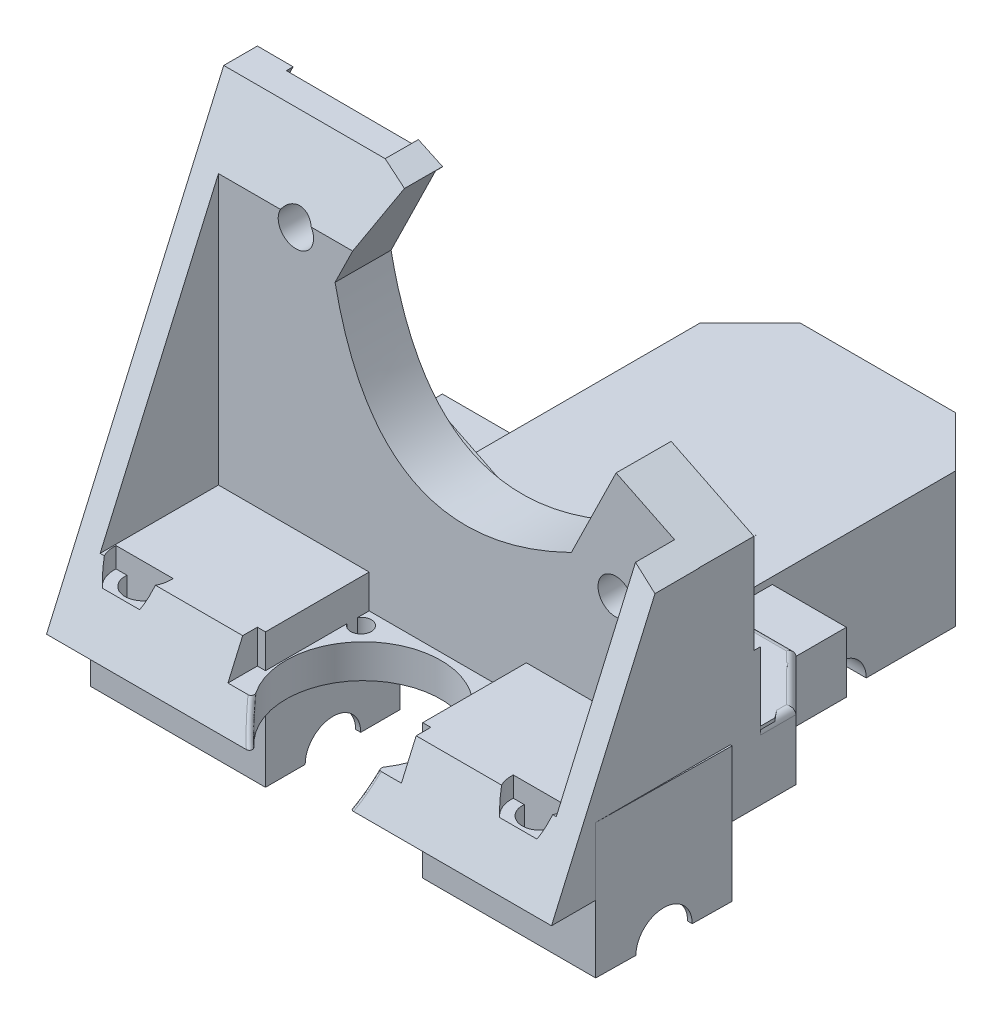
SolidWorks part; units mm, degrees
ref_plane "Front Plane" through (0, 0, 0) normal (0, 0, 1) x (1, 0, 0)
ref_plane "Top Plane" through (0, 0, 0) normal (0, 1, 0) x (1, 0, 0)
ref_plane "Right Plane" through (0, 0, 0) normal (1, 0, 0) x (0, 0, -1)
sketch "Sketch1" plane through (0, 0, 0) normal (0, 1, 0) x (1, 0, 0)
  line L0 (-36.3571, 0) -> (-17.8571, 0)
  line L1 (-36.3571, -43.7952) -> (38.6429, -43.7952)
  line L2 (-36.3571, -43.7952) -> (-36.3571, 0)
  line L3 (-17.8571, 42.2048) -> (20.1429, 42.2048)
  line L4 (38.6429, -43.7952) -> (38.6429, 0)
  line L5 (-36.3571, -43.7952) -> (20.1429, 24.2638) construction
  line L6 (-17.8571, 20.2381) -> (38.6429, -43.7952) construction
  line L7 (-17.8571, 0) -> (-17.8571, 42.2048)
  line L8 (38.6429, 0) -> (20.1429, 0)
  line L9 (20.1429, 0) -> (20.1429, 42.2048)
  line L10 (1.1429, 42.2048) -> (1.1429, -43.7952) construction
  point P0 (0, 0)
  dimension "D1" = 75
  dimension "D2" = 86
  dimension "D3" = 38
  dimension "D4" = 18.5
extrude "Boss-Extrude1" add sketch "Sketch1" along normal blind 10
sketch "Sketch2" plane through (0, 10, 0) normal (0, 1, 0) x (1, 0, 0)
  line L0 (-17.8571, 42.2048) -> (-17.8571, 0) construction
  line L1 (-16.3571, 21) -> (18.6429, 21) construction
  line L2 (11.6429, 41) -> (11.6429, 35.2097) construction
  line L3 (-9.3571, 41) -> (-9.3571, 35.5) construction
  line L4 (2.1863, 41) -> (-16.3571, 41) construction
  line L5 (-16.3571, 41) -> (-16.3571, 1) construction
  line L6 (-16.3571, 1) -> (18.6429, 1) construction
  line L7 (18.6429, 1) -> (18.6429, 41) construction
  line L8 (18.6429, 41) -> (2.1863, 41) construction
  line L9 (11.6429, 1) -> (11.6429, 6.7903) construction
  line L10 (-9.3571, 1) -> (-9.3571, 6.5) construction
  line L11 (-17.8571, 0) -> (-36.3571, 0) construction
  circle A0 centre (-9.3571, 35.5) radius 2.625
  circle A1 centre (-9.3571, 6.5) radius 2.625
  circle A2 centre (11.6429, 6.7903) radius 2.625
  circle A3 centre (11.6429, 35.2097) radius 2.625
  dimension "D7" = 5.25
  dimension "D8" = 5.25
  dimension "D9" = 5.25
  dimension "D10" = 5.25
  dimension "D1" = 40
  dimension "D2" = 35
  dimension "D3" = 1.5
  dimension "D4" = 5.5
  dimension "D5" = 7
  dimension "D6" = 7
  dimension "D11" = 1
extrude "Cut-Extrude1" cut sketch "Sketch2" against normal through all
sketch "Sketch5" plane through (0, 10, 0) normal (0, 1, 0) x (1, 0, 0)
  line L0 (-17.8571, 0) -> (-17.8571, -3) construction
  line L1 (-0.3571, -3) -> (-35.3571, -3) construction
  line L2 (-35.3571, -3) -> (-35.3571, -43) construction
  line L3 (-35.3571, -43) -> (-0.3571, -43) construction
  line L4 (2.6429, -43) -> (2.6429, -3) construction
  line L5 (2.6429, -43) -> (37.6429, -43) construction
  line L6 (20.1429, 0) -> (20.1429, -3) construction
  line L8 (-0.3571, -43) -> (-0.3571, -3) construction
  line L9 (-36.3571, 0) -> (-36.3571, -43.7952) construction
  line L10 (37.6429, -3) -> (37.6429, -43) construction
  line L11 (2.6429, -3) -> (37.6429, -3) construction
  line L12 (38.6429, -43.7952) -> (38.6429, 0) construction
  line L14 (-28.3571, -3) -> (-28.3571, -8.5) construction
  line L15 (-7.3571, -3) -> (-7.3571, -8.5) construction
  line L16 (9.6429, -3) -> (9.6429, -8.5) construction
  line L17 (30.6429, -3) -> (30.6429, -8.5) construction
  line L18 (-35.3571, -23) -> (37.6429, -23) construction
  line L19 (30.6429, -43) -> (30.6429, -37.5) construction
  line L20 (9.6429, -43) -> (9.6429, -37.5) construction
  line L21 (-7.3571, -43) -> (-7.3571, -37.5) construction
  line L22 (-28.3571, -43) -> (-28.3571, -37.5) construction
  circle A0 centre (-28.3571, -8.5) radius 2.625
  circle A1 centre (-7.3571, -8.5) radius 2.625
  circle A2 centre (9.6429, -8.5) radius 2.625
  circle A3 centre (30.6429, -8.5) radius 2.625
  circle A4 centre (30.6429, -37.5) radius 2.625
  circle A5 centre (9.6429, -37.5) radius 2.625
  circle A6 centre (-7.3571, -37.5) radius 2.625
  circle A7 centre (-28.3571, -37.5) radius 2.625
  dimension "D17" = 5.25
  dimension "D18" = 5.25
  dimension "D19" = 5.25
  dimension "D20" = 5.25
  dimension "D1" = 3
  dimension "D2" = 40
  dimension "D3" = 40
  dimension "D4" = 3
  dimension "D5" = 35
  dimension "D6" = 35
  dimension "D7" = 1
  dimension "D8" = 1
  dimension "D9" = 5.5
  dimension "D10" = 5.5
  dimension "D11" = 5.5
  dimension "D12" = 5.5
  dimension "D13" = 7
  dimension "D14" = 7
  dimension "D15" = 7
  dimension "D16" = 7
extrude "Cut-Extrude2" cut sketch "Sketch5" against normal through all
sketch "Sketch7" plane through (0, 10, 0) normal (0, 1, 0) x (1, 0, 0)
  line L1 (-36.3571, -12.4772) -> (38.6429, -12.7296)
  line L2 (-36.3571, -12.4772) -> (-36.3571, -21.8366)
  line L3 (-36.3571, -21.8366) -> (38.6429, -21.8366)
  line L4 (38.6429, -12.7296) -> (38.6429, -21.8366)
  line L5 (38.6429, -43.7952) -> (38.6429, 0) construction
extrude "Boss-Extrude2" add sketch "Sketch7" along normal blind 50
sketch "Sketch8" plane through (-0.0424, 0, 12.5994) normal (0.0034, 0, -1) x (-1, 0, -0.0034)
  line L0 (-31.9124, 60) -> (-31.9124, 38.3732) construction
  line L1 (-38.6855, 60) -> (36.3149, 60) construction
  line L2 (0, 60) -> (0, 10) construction
  line L3 (-20.0007, 10) -> (17.9991, 10) construction
  line L4 (-31.9124, 38.3732) -> (27.3877, 67.3662)
  line L5 (27.3877, 67.3662) -> (35.5135, 50.7463)
  line L6 (30.9221, 37.3702) -> (-22.9803, 11.0163)
  line L7 (-36.3563, 15.6077) -> (-44.4821, 32.2276)
  line L8 (-44.4821, 32.2276) -> (-31.9124, 38.3732)
  line L9 (-38.6855, 10) -> (36.3149, 10) construction
  arc A1 (-22.9803, 11.0163) -> (-36.3563, 15.6077) centre (-27.3726, 20) cw
  arc A2 (35.5135, 50.7463) -> (30.9221, 37.3702) centre (26.5298, 46.3539) cw
  dimension "D1" = 10
  dimension "D2" = 10
  dimension "D3" = 80
  dimension "D4" = 28.5
extrude "Cut-Extrude3" cut sketch "Sketch8" against normal blind 1
sketch "Sketch9" plane through (-0.0458, 0, 13.5994) normal (0.0034, 0, -1) x (-1, 0, -0.0034)
  line L1 (12.3215, 60) -> (-38.6888, 35.06) construction
  line L2 (-9.0128, 49.5692) -> (1.4284, 22.9502) construction
  line L3 (-22.9803, 11.0163) -> (30.9221, 37.3702) construction
  line L9 (33.537, 54.789) -> (21.2078, 48.761) construction
  line L10 (35.5135, 50.7463) -> (30.9892, 60) construction
  circle A0 centre (-26.291, 25.1554) radius 2.625
  circle A1 centre (21.2078, 48.761) radius 2.625
  circle A2 centre (-3.7922, 36.2597) radius 10
  dimension "D5" = 5.25
  dimension "D6" = 5.25
  dimension "D8" = 20
  dimension "D1" = 25
  dimension "D4" = 14
  dimension "D7" = 25
extrude "Cut-Extrude4" cut sketch "Sketch9" against normal through all
chamfer "Chamfer1" distance 7.5 angle 45 4 edges at (20.1429, 5, -42.2048) (-17.8571, 5, -42.2048) (38.6429, 5, 0) (-36.3571, 5, 0)
fillet "Fillet3" radius 1 11 edges at (34.8929, 10, 3.75) (25.6429, 10, 0) (20.1429, 10, -17.3524) (16.3929, 10, -38.4548) (1.1429, 10, -42.2048) (-14.1071, 10, -38.4548) (-17.8571, 10, -17.3524) (-23.3571, 10, 0) (-32.6071, 10, 3.75)
sketch "Sketch15" plane through (0, 10, 0) normal (0, 1, 0) x (1, 0, 0)
  circle A0 centre (-9.3571, 35.5) radius 4.25
  circle A1 centre (11.6429, 35.2097) radius 4.25
  circle A2 centre (-9.3571, 6.5) radius 4.25
  circle A3 centre (11.6429, 6.7903) radius 4.25
  circle A4 centre (-28.3571, -8.5) radius 4.25
  circle A5 centre (-7.3571, -8.5) radius 4.25
  circle A6 centre (9.6429, -8.5) radius 4.25
  circle A7 centre (30.6429, -8.5) radius 4.25
  circle A8 centre (-28.3571, -37.5) radius 4.25
  circle A9 centre (-7.3571, -37.5) radius 4.25
  circle A10 centre (9.6429, -37.5) radius 4.25
  circle A11 centre (30.6429, -37.5) radius 4.25
  dimension "D1" = 8.5
  dimension "D2" = 8.5
  dimension "D3" = 8.5
  dimension "D4" = 8.5
  dimension "D5" = 8.5
  dimension "D6" = 8.5
  dimension "D7" = 8.5
  dimension "D8" = 8.5
  dimension "D9" = 8.5
  dimension "D10" = 8.5
  dimension "D11" = 8.5
  dimension "D12" = 8.5
extrude "Cut-Extrude9" cut sketch "Sketch15" against normal blind 3
sketch "Sketch16" plane through (20.1429, 0, 0) normal (1, 0, 0) x (0, 0, -1)
  line L0 (0, 9) -> (0, 0) construction
  line L1 (0, 9) -> (7.5, 9)
  line L2 (0, 9) -> (0, 0)
  line L3 (0, 0) -> (7.5, 0)
  line L4 (7.5, 9) -> (7.5, 0)
  line L5 (0, 0) -> (34.7048, 0) construction
  line L6 (-7.5, 0) -> (-7.5, 9) construction
  dimension "D1" = 15
extrude "Boss-Extrude6" add sketch "Sketch16" along normal blind 11
sketch "Sketch17" plane through (-17.8571, 0, 0) normal (-1, 0, 0) x (0, 0, 1)
  line L1 (0, 9) -> (-7.5, 9)
  line L2 (0, 9) -> (0, 0)
  line L3 (0, 0) -> (-7.5, 0)
  line L4 (-7.5, 9) -> (-7.5, 0)
extrude "Boss-Extrude9" add sketch "Sketch17" along normal blind 11
sketch "Sketch21" plane through (0, 0, 0) normal (0, -1, 0) x (1, 0, 0)
  line L0 (31.1429, -7.5) -> (20.1429, -7.5) construction
  line L1 (-19.8571, -4.5) -> (-25.8571, -4.5)
  line L2 (-19.8571, -4.5) -> (-19.8571, -1.5)
  line L3 (-19.8571, -1.5) -> (-25.8571, -1.5)
  line L4 (-25.8571, -4.5) -> (-25.8571, -1.5)
  line L5 (28.1429, -4.5) -> (22.1429, -4.5)
  line L6 (28.1429, -4.5) -> (28.1429, -1.5)
  line L7 (28.1429, -1.5) -> (22.1429, -1.5)
  line L8 (22.1429, -4.5) -> (22.1429, -1.5)
  line L9 (31.1429, 0) -> (31.1429, -7.5) construction
  line L10 (-28.8571, -7.5) -> (-17.8571, -7.5) construction
  line L11 (-28.8571, -7.5) -> (-28.8571, 0) construction
  dimension "D1" = 6
  dimension "D2" = 3
  dimension "D3" = 3
  dimension "D4" = 3
  dimension "D5" = 3
  dimension "D6" = 3
  dimension "D7" = 6
  dimension "D8" = 3
extrude "Cut-Extrude11" cut sketch "Sketch21" against normal blind 7
sketch "Sketch22" plane through (0, 0, -7.5) normal (0, 0, -1) x (-1, 0, 0)
  line L0 (-25.1429, 0) -> (-25.1429, 3.5) construction
  line L1 (-31.1429, 0) -> (-20.1429, 0) construction
  line L2 (22.8571, 0) -> (22.8571, 3.5) construction
  line L3 (28.8571, 0) -> (17.8571, 0) construction
  line L4 (17.8571, 9) -> (17.8571, 0) construction
  line L5 (-20.1429, 0) -> (-20.1429, 9) construction
  circle A0 centre (-25.1429, 3.5) radius 1.6
  circle A1 centre (22.8571, 3.5) radius 1.6
  dimension "D2" = 3.2
  dimension "D3" = 3.2
  dimension "D1" = 3.5
  dimension "D4" = 5
  dimension "D5" = 5
extrude "Cut-Extrude12" cut sketch "Sketch22" against normal blind 10
sketch "Sketch23" plane through (-0.0424, 0, 12.5994) normal (0.0034, 0, -1) x (-1, 0, -0.0034)
  line L0 (-19.7058, 27.5293) -> (15.3861, 44.7339)
  line L1 (-19.7058, 27.5293) -> (-26.3545, 41.0905)
  line L2 (15.3861, 44.7339) -> (8.7184, 58.3339)
  line L3 (-36.682, 62.706) -> (-2.1412, 79.6404)
  line L4 (-26.3545, 41.0905) -> (-38.6855, 35.0617)
  line L5 (12.3215, 60) -> (-38.6855, 35.0617) construction
  line L7 (-39.9267, 60.8454) -> (-36.682, 62.706)
  line L8 (8.7184, 58.3339) -> (12.3215, 60)
  line L9 (12.3215, 60) -> (-2.1412, 79.6404)
  line L10 (-38.6855, 35.0617) -> (-53.5634, 52.4403)
  line L11 (-53.5634, 52.4403) -> (-39.9267, 60.8454)
  circle A0 centre (-26.291, 25.1554) radius 2.625 construction
  circle A1 centre (21.2078, 48.761) radius 2.625 construction
  dimension "D1" = 7
  dimension "D2" = 7
extrude "Cut-Extrude15" cut sketch "Sketch23" against normal blind 10
sketch "Sketch24" plane through (-0.0458, 0, 13.5994) normal (0.0034, 0, -1) x (-1, 0, -0.0034)
  line L0 (15.3861, 44.7339) -> (-19.7058, 27.5293)
  spline S0 degree 2 poles (15.3861, 44.7339) (8.9579, 13.4549) (-19.7058, 27.5293) knots 0 0 0 1 1 1
extrude "Cut-Extrude16" cut sketch "Sketch24" against normal blind 10
sketch "Sketch25" plane through (0, 10, 0) normal (0, 1, 0) x (1, 0, 0)
  line L0 (-36.3571, -21.8366) -> (38.6429, -21.8366) construction
  line L1 (-36.3571, -43.7952) -> (-32.7766, -43.7952)
  line L2 (-36.3571, -43.7952) -> (-36.3571, -21.8366)
  line L3 (-36.3571, -21.8366) -> (-32.7766, -21.8366)
  line L4 (-32.7766, -43.7952) -> (-32.7766, -21.8366)
  line L5 (1.1429, -43.7952) -> (1.1429, -21.8366) construction
  line L6 (-36.3571, -43.7952) -> (38.6429, -43.7952) construction
extrude "Boss-Extrude10" add sketch "Sketch25" along normal up to surface (50 mm away) up to face at (-26.5905, 60, 15.9498)
sketch "Sketch26" plane through (0, 10, 0) normal (0, 1, 0) x (1, 0, 0)
  line L0 (-32.7766, -21.8366) -> (38.6429, -21.8366) construction
  line L1 (38.6429, -43.7952) -> (34.9637, -43.7952)
  line L2 (38.6429, -43.7952) -> (38.6429, -21.8366)
  line L3 (38.6429, -21.8366) -> (34.9637, -21.8366)
  line L4 (34.9637, -43.7952) -> (34.9637, -21.8366)
extrude "Boss-Extrude11" add sketch "Sketch26" along normal up to surface (26.8094 mm away) up to face at (32.4604, 38.0761, 17.7727)
sketch "Sketch28" plane through (-36.3571, 0, 0) normal (-1, 0, 0) x (0, 0, 1)
  line L0 (17.4772, 60) -> (43.7952, 0)
  line L1 (12.4772, 60) -> (43.7952, 60) construction
  line L2 (7.5, 0) -> (43.7952, 0) construction
  line L3 (43.7952, 60) -> (43.7952, 0) construction
  line L4 (43.7952, 0) -> (43.7952, 60)
  line L5 (43.7952, 60) -> (17.4772, 60)
  dimension "D1" = 5
extrude "Cut-Extrude17" cut sketch "Sketch28" against normal through all
sketch "Sketch29" plane through (0, 10, 0) normal (0, 1, 0) x (1, 0, 0)
  line L0 (-32.7766, -21.8366) -> (34.9637, -21.8366) construction
  line L1 (-11.6071, -40.976) -> (14.1585, -40.976)
  line L2 (-11.6071, -40.976) -> (-11.6071, -21.8366)
  line L3 (-11.6071, -21.8366) -> (14.1585, -21.8366)
  line L4 (14.1585, -40.976) -> (14.1585, -21.8366)
extrude "Boss-Extrude12" add sketch "Sketch29" against normal up to surface (10 mm away) up to face at (25.1429, 0, -3)
sketch "Sketch31" plane through (0, 10, 0) normal (0, 1, 0) x (1, 0, 0)
  line L0 (-32.7766, -21.8366) -> (34.9637, -21.8366) construction
  line L1 (-11.6071, -21.8366) -> (14.1585, -21.8366) construction
  line L2 (-11.6071, -21.8366) -> (-11.6071, -46.8921) construction
  line L3 (-11.6071, -46.8921) -> (14.1585, -46.8921) construction
  line L4 (14.1585, -21.8366) -> (14.1585, -46.8921) construction
  line L5 (-11.6071, -21.8366) -> (-9.1071, -24.3366) construction
  line L6 (14.1585, -21.8366) -> (11.6585, -24.3366) construction
  line L7 (1.2757, -21.8366) -> (1.2757, -46.8921) construction
  circle A0 centre (-9.1071, -24.3366) radius 1.525
  circle A1 centre (11.6585, -24.3366) radius 1.525
  circle A2 centre (1.2757, -34.3644) radius 11.5
  dimension "D1" = 2.5
  dimension "D5" = 3.05
  dimension "D6" = 3.05
  dimension "D7" = 23
  dimension "D2" = 2.5
  dimension "D3" = 2.5
  dimension "D4" = 2.5
extrude "Cut-Extrude19" cut sketch "Sketch31" against normal through all
sketch "Sketch32" plane through (0, 10, 0) normal (0, 1, 0) x (1, 0, 0)
  line L0 (-32.7766, -21.8366) -> (34.9637, -21.8366) construction
  line L1 (-11.6071, -43.1878) -> (14.1585, -43.0827)
  line L2 (-11.6071, -43.1878) -> (-11.6071, -21.8366)
  line L3 (-11.6071, -21.8366) -> (14.1585, -21.8366)
  line L4 (14.1585, -43.0827) -> (14.1585, -21.8366)
extrude "Cut-Extrude20" cut sketch "Sketch32" against normal blind 5
fillet "Fillet4" radius 0.5 2 edges at (-6.5603, 2.3112, 42.7815) (9.1116, 2.3112, 42.7815)
sketch "Sketch33" plane through (0, 0, 0) normal (0, -1, 0) x (1, 0, 0)
  line L0 (12.6429, -42.2048) -> (20.1429, -34.7048) construction
  line L1 (-17.8571, 0) -> (20.1429, 0)
  line L2 (-17.8571, 0) -> (-17.8571, -34.7048)
  line L4 (20.1429, 0) -> (20.1429, -34.7048)
  line L5 (-17.8571, -34.7048) -> (-10.3571, -42.2048)
  line L6 (-10.3571, -42.2048) -> (12.6429, -42.2048)
  line L7 (12.6429, -42.2048) -> (20.1429, -34.7048)
extrude "Boss-Extrude13" add sketch "Sketch33" along normal mid plane 20
sketch "Sketch34" plane through (0, -10, 0) normal (0, -1, 0) x (1, 0, 0)
  line L0 (1.1429, 0) -> (1.1429, -42.2048) construction
  line L1 (-10.911, -17.3235) -> (13.189, -17.3235)
  line L2 (-10.911, -17.3235) -> (-10.911, -9.9585)
  line L3 (-10.911, -9.9585) -> (13.189, -9.9585)
  line L4 (13.189, -17.3235) -> (13.189, -9.9585)
  line L5 (-10.911, -17.3235) -> (13.189, -9.9585) construction
  line L6 (-10.911, -9.9585) -> (13.189, -17.3235) construction
  line L7 (20.1429, 0) -> (-17.8571, 0) construction
  line L8 (-10.3571, -42.2048) -> (12.6429, -42.2048) construction
  line L9 (-17.8571, -17.3524) -> (20.1429, -17.3524) construction
  line L10 (-17.8571, 0) -> (-17.8571, -34.7048) construction
  line L11 (20.1429, -34.7048) -> (20.1429, 0) construction
  point P0 (1.1429, -17.3524)
  dimension "D2" = 24.1
revolve "Cut-Revolve1" cut sketch "Sketch34" angle 360 about L1
sketch "Sketch35" plane through (-10.911, 0, 0) normal (1, 0, 0) x (0, 0, -1)
  line L0 (24.6885, -10) -> (9.9585, -10) construction
  circle A0 centre (17.3235, -10) radius 4.125
  dimension "D1" = 8.25
extrude "Cut-Extrude22" cut sketch "Sketch35" against normal through all both and the other way through all
sketch "Sketch36" plane through (0, -10, 0) normal (0, -1, 0) x (1, 0, 0)
  line L0 (1.139, -24.6885) -> (1.139, -42.2048) construction
  line L1 (13.189, -24.6885) -> (-10.911, -24.6885) construction
  line L2 (-10.3571, -42.2048) -> (12.6429, -42.2048) construction
  line L3 (7.139, -27.0919) -> (-4.861, -27.0919) construction
  line L4 (9.639, -28.0919) -> (9.639, -26.0919)
  line L5 (-7.361, -28.0919) -> (-2.361, -28.0919)
  line L6 (-7.361, -28.0919) -> (-7.361, -26.0919)
  line L7 (-7.361, -26.0919) -> (-2.361, -26.0919)
  line L8 (-2.361, -28.0919) -> (-2.361, -26.0919)
  line L9 (-7.361, -28.0919) -> (-2.361, -26.0919) construction
  line L10 (-7.361, -26.0919) -> (-2.361, -28.0919) construction
  line L11 (4.639, -28.0919) -> (4.639, -26.0919)
  line L12 (9.639, -28.0919) -> (4.639, -28.0919)
  line L13 (9.639, -26.0919) -> (4.639, -26.0919)
  line L14 (20.1429, -17.3235) -> (-17.8571, -17.3235) construction
  line L15 (20.1429, -21.4485) -> (20.1429, -13.1985) construction
  line L16 (-17.8571, -13.1985) -> (-17.8571, -21.4485) construction
  line L17 (-7.361, -8.5551) -> (-2.361, -6.5551) construction
  line L18 (-7.361, -6.5551) -> (-2.361, -8.5551) construction
  line L19 (7.139, -7.5551) -> (-4.861, -7.5551) construction
  line L20 (9.639, -8.5551) -> (4.639, -8.5551)
  line L21 (9.639, -6.5551) -> (4.639, -6.5551)
  line L22 (4.639, -6.5551) -> (4.639, -8.5551)
  line L23 (-2.361, -6.5551) -> (-2.361, -8.5551)
  line L24 (-7.361, -8.5551) -> (-2.361, -8.5551)
  line L25 (-7.361, -6.5551) -> (-7.361, -8.5551)
  line L26 (-7.361, -6.5551) -> (-2.361, -6.5551)
  line L27 (9.639, -6.5551) -> (9.639, -8.5551)
  point P9 (1.139, -27.0919)
  point P33 (1.139, -7.5551)
  dimension "D1" = 12
  dimension "D2" = 5
  dimension "D3" = 2
revolve "Cut-Revolve2" cut sketch "Sketch36" angle 360 about L14
sketch "Sketch37" plane through (0, 0, 0) normal (0, -1, 0) x (1, 0, 0)
  line L0 (1.2757, 17.1469) -> (1.2757, 43.7952) construction
  line L1 (-36.3571, 37.2304) -> (-10.4001, 37.2304)
  line L2 (-36.3571, 37.2304) -> (-36.3571, 17.2304)
  line L3 (-36.3571, 17.2304) -> (-10.4001, 17.2304)
  line L4 (-10.4001, 37.2304) -> (-10.4001, 17.2304)
  line L5 (12.9514, 37.2304) -> (12.9514, 17.2304)
  line L6 (38.9085, 17.2304) -> (12.9514, 17.2304)
  line L7 (38.6429, 37.2304) -> (38.9085, 17.2304)
  line L8 (38.6429, 37.2304) -> (12.9514, 37.2304)
  line L9 (38.6429, 43.7952) -> (38.6429, 7.5) construction
  line L10 (-36.3571, 27.2304) -> (38.7757, 27.2304) construction
  line L11 (-18.2985, -17.7696) -> (20.459, -17.7696) construction
  dimension "D1" = 20
  dimension "D2" = 20
  dimension "D3" = 45
extrude "Boss-Extrude14" add sketch "Sketch37" along normal mid plane 20
sketch "Sketch38" plane through (0, 0, 0) normal (0, -1, 0) x (1, 0, 0)
  line L1 (-35.0919, 13.5734) -> (38.4876, 13.5734)
  line L2 (-35.0919, 13.5734) -> (-35.0919, 6.8188)
  line L3 (-31.3243, 2.4672) -> (32.4351, 2.4672)
  line L4 (38.4876, 13.5734) -> (38.4876, 10.459)
  line L7 (-35.0919, 6.8188) -> (-31.3243, 2.4672)
  line L8 (-36.3571, 7.5) -> (-28.8571, 0) construction
  line L9 (32.4351, 2.4672) -> (38.4876, 10.459)
extrude "Boss-Extrude15" add sketch "Sketch38" against normal up to surface (10 mm away) up to face at (3.4801, 10, -1.1428)
sketch "Sketch39" plane through (0, -10, 0) normal (0, -1, 0) x (1, 0, 0)
  line L0 (-23.3786, 37.2304) -> (-23.3786, 17.2304) construction
  line L1 (-10.4001, 37.2304) -> (-36.3571, 37.2304) construction
  line L2 (-36.3571, 17.2304) -> (-10.4001, 17.2304) construction
  line L3 (-10.4001, 27.2304) -> (-36.3571, 27.2304) construction
  line L4 (-10.4001, 17.2304) -> (-10.4001, 37.2304) construction
  line L5 (-36.3571, 37.2304) -> (-36.3571, 17.2304) construction
  line L6 (1.2757, 22.8644) -> (1.2757, 38.161) construction
  line L7 (-35.602, 27.21) -> (-11.1552, 27.21)
  line L8 (-35.602, 27.21) -> (-35.602, 35.004)
  line L9 (-35.602, 35.004) -> (-11.1552, 35.004)
  line L10 (-11.1552, 27.21) -> (-11.1552, 35.004)
  line L11 (-35.602, 27.21) -> (-11.1552, 35.004) construction
  line L12 (-35.602, 35.004) -> (-11.1552, 27.21) construction
  line L13 (38.1533, 35.004) -> (13.7065, 27.21) construction
  line L14 (38.1533, 27.21) -> (13.7065, 35.004) construction
  line L15 (12.9514, 27.2304) -> (38.9085, 27.2304) construction
  line L16 (13.7065, 27.21) -> (13.7065, 35.004)
  line L17 (38.1533, 35.004) -> (13.7065, 35.004)
  line L18 (38.1533, 27.21) -> (38.1533, 35.004)
  line L19 (38.1533, 27.21) -> (13.7065, 27.21)
  arc A0 (-6.4542, 42.879) -> (9.0055, 42.879) centre (1.2757, 34.3644) ccw construction
  point P12 (-23.3786, 27.2304)
  point P29 (25.9299, 27.2304)
  dimension "D1" = 24.4468
revolve "Cut-Revolve3" cut sketch "Sketch39" angle 360 about L7
sketch "Sketch40" plane through (0, -10, 0) normal (0, -1, 0) x (1, 0, 0)
  line L0 (-23.3786, 37.2304) -> (-23.3786, 35.004) construction
  line L1 (-10.4001, 37.2304) -> (-36.3571, 37.2304) construction
  line L2 (-35.602, 35.004) -> (-11.1552, 35.004) construction
  line L3 (-17.3882, 36.1172) -> (-29.3691, 36.1172) construction
  line L4 (-36.3571, 27.2304) -> (-10.4001, 27.2304) construction
  line L5 (-36.3571, 37.2304) -> (-36.3571, 17.2304) construction
  line L6 (-10.4001, 17.2304) -> (-10.4001, 37.2304) construction
  line L7 (-14.8882, 36.7172) -> (-19.8882, 35.5172) construction
  line L8 (-31.8691, 35.5172) -> (-26.8691, 35.5172)
  line L9 (-31.8691, 35.5172) -> (-31.8691, 36.7172)
  line L10 (-31.8691, 36.7172) -> (-26.8691, 36.7172)
  line L11 (-26.8691, 35.5172) -> (-26.8691, 36.7172)
  line L12 (-31.8691, 35.5172) -> (-26.8691, 36.7172) construction
  line L13 (-31.8691, 36.7172) -> (-26.8691, 35.5172) construction
  line L14 (-14.8882, 35.5172) -> (-19.8882, 36.7172) construction
  line L15 (-19.8882, 35.5172) -> (-19.8882, 36.7172)
  line L16 (-14.8882, 36.7172) -> (-19.8882, 36.7172)
  line L17 (-14.8882, 35.5172) -> (-14.8882, 36.7172)
  line L18 (-14.8882, 35.5172) -> (-19.8882, 35.5172)
  line L19 (1.2757, 34.3644) -> (1.2757, 16.2765) construction
  line L20 (17.4395, 35.5172) -> (22.4395, 36.7172) construction
  line L21 (34.4204, 36.7172) -> (29.4204, 35.5172) construction
  line L22 (34.4204, 35.5172) -> (29.4204, 36.7172) construction
  line L23 (17.4395, 36.7172) -> (22.4395, 35.5172) construction
  line L24 (19.9395, 36.1172) -> (31.9204, 36.1172) construction
  line L25 (25.9299, 37.2304) -> (25.9299, 35.004) construction
  line L26 (17.4395, 35.5172) -> (22.4395, 35.5172)
  line L27 (17.4395, 35.5172) -> (17.4395, 36.7172)
  line L28 (17.4395, 36.7172) -> (22.4395, 36.7172)
  line L29 (22.4395, 35.5172) -> (22.4395, 36.7172)
  line L30 (29.4204, 35.5172) -> (29.4204, 36.7172)
  line L31 (34.4204, 36.7172) -> (29.4204, 36.7172)
  line L32 (34.4204, 35.5172) -> (34.4204, 36.7172)
  line L33 (34.4204, 35.5172) -> (29.4204, 35.5172)
  point P9 (-23.3786, 36.1172)
  point P26 (0, 0)
  point P38 (25.9299, 36.1172)
  dimension "D1" = 5
  dimension "D2" = 1.2
revolve "Cut-Revolve4" cut sketch "Sketch40" angle 360 about L4
sketch "Sketch41" plane through (-35.602, 0, 0) normal (1, 0, 0) x (0, 0, -1)
  line L0 (-19.4161, -10) -> (-35.004, -10) construction
  circle A0 centre (-27.21, -10) radius 4.125
  dimension "D1" = 8.25
extrude "Cut-Extrude23" cut sketch "Sketch41" against normal through all both and the other way through all
